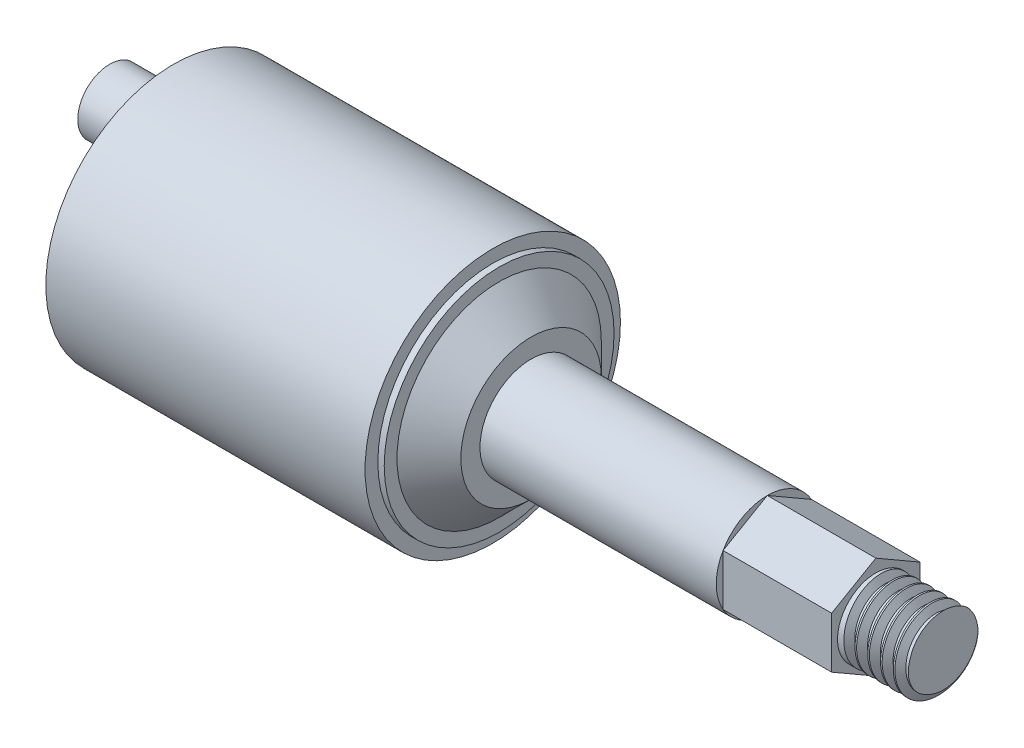
SolidWorks part; units mm, degrees
ref_plane "Front Plane" through (0, 0, 0) normal (0, 0, 1) x (1, 0, 0)
ref_plane "Top Plane" through (0, 0, 0) normal (0, 1, 0) x (1, 0, 0)
ref_plane "Right Plane" through (0, 0, 0) normal (1, 0, 0) x (0, 0, -1)
sketch "Sketch1" plane through (0, 0, 0) normal (1, 0, 0) x (0, 0, -1)
  circle A0 centre (0, 0) radius 20
extrude "Boss-Extrude1" add sketch "Sketch1" along normal blind 50
sketch "Sketch2" plane through (0, 0, 0) normal (-1, 0, 0) x (0, 0, 1)
  circle A0 centre (0, 10) radius 5
  circle A1 centre (0, -10) radius 5
  dimension "D1" = 10
  dimension "D2" = 10
extrude "Boss-Extrude2" add sketch "Sketch2" along normal blind 10
sketch "Sketch3" plane through (50, 0, 0) normal (1, 0, 0) x (0, 0, -1)
  circle A0 centre (0, 0) radius 18
extrude "Boss-Extrude3" add sketch "Sketch3" along normal blind 1
sketch "Sketch4" plane through (51, 0, 0) normal (1, 0, 0) x (0, 0, -1)
  circle A2 centre (0, 0) radius 16
  circle A3 centre (0, 0) radius 16
  dimension "D1" = 2
extrude "Boss-Extrude4" add sketch "Sketch4" along normal blind 5 draft 45
sketch "Sketch5" plane through (56, 0, 0) normal (1, 0, 0) x (0, 0, -1)
  circle A0 centre (0, 0) radius 8
  dimension "D1" = 16
extrude "Boss-Extrude5" add sketch "Sketch5" along normal blind 37
sketch "Sketch6" plane through (93, 0, 0) normal (1, 0, 0) x (0, 0, -1)
  line L1 (6.9282, 4) -> (0, 8)
  line L2 (0, 8) -> (-6.9282, 4)
  line L3 (-6.9282, 4) -> (-6.9282, -4)
  line L4 (-6.9282, -4) -> (0, -8)
  line L5 (0, -8) -> (6.9282, -4)
  line L6 (6.9282, -4) -> (6.9282, 4)
  circle A0 centre (0, 0) radius 8 construction
  dimension "D1" = 16
extrude "Boss-Extrude6" add sketch "Sketch6" along normal blind 17
sketch "Sketch7" plane through (110, 0, 0) normal (1, 0, 0) x (0, 0, -1)
  circle A0 centre (0, 0) radius 6
  dimension "D1" = 12
extrude "Boss-Extrude7" add sketch "Sketch7" along normal blind 10
thread "Thread1" pitch 2 method cut profile "Thread Profile1" start angle 0, offset 0, length 0, pitch 2, diameter 12
ref_plane "Plane1" through (110, 0, -6) normal (0, -1, 0) x (0, 0, -1)
sketch "Thread Profile1" plane through (110, 0, -6) normal (0, -1, 0) x (0, 0, -1)
  line L0 (0, 0) -> (0, 2) construction
  line L11 (0, 0) -> (0, 1.75)
  line L12 (0, 1.75) -> (-1.0825, 1.125)
  line L13 (-1.0825, 1.125) -> (-1.0825, 0.625)
  line L15 (-1.0825, 0.625) -> (0, 0)
  line L17 (-1.0825, 0.875) -> (0, 0.875) construction
  point P2 (0, 0)
  dimension "Pitch" = 2
  dimension "Profile_Angle" = 60
  dimension "Profile_Land" = 0.5
  dimension "Profile_Height" = 1.0825
